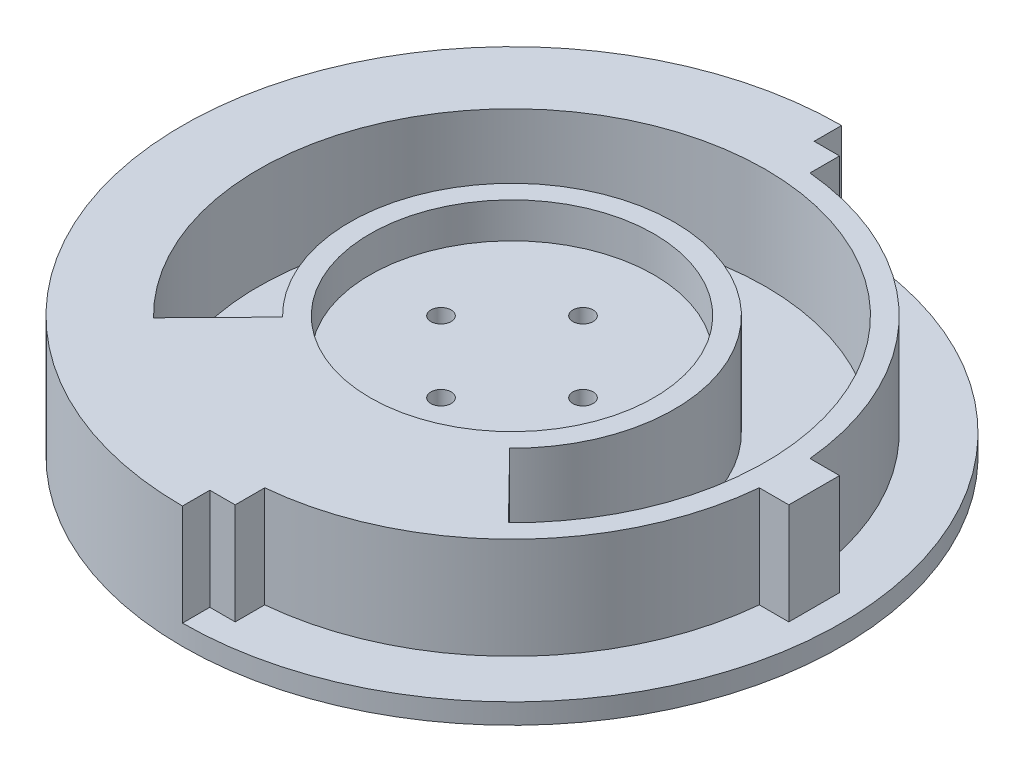
SolidWorks part; units mm, degrees
ref_plane "Front Plane" through (0, 0, 0) normal (0, 0, 1) x (1, 0, 0)
ref_plane "Top Plane" through (0, 0, 0) normal (0, 1, 0) x (1, 0, 0)
ref_plane "Right Plane" through (0, 0, 0) normal (1, 0, 0) x (0, 0, -1)
sketch "Sketch1" plane through (0, 0, 0) normal (0, 1, 0) x (1, 0, 0)
  line L0 (-17.5, -17.8536) -> (-11.2, -11.4263)
  line L1 (0, -55) -> (0, 55) construction
  line L2 (17.5, -17.8536) -> (11.2, -11.4263)
  line L4 (-17.5, -17.8536) -> (3.8221, -38.7535) construction
  circle A0 centre (0, 0) radius 27
  arc A1 (11.2, -11.4263) -> (-11.2, -11.4263) centre (0, 0) ccw
  arc A2 (17.5, -17.8536) -> (-17.5, -17.8536) centre (0, 0) ccw
  circle A3 centre (0, 0) radius 14
  arc A4 (16.5039, 11.7639) -> (14.35, -14.6399) centre (0.1913, -0.1952) cw construction
  circle A5 centre (0, 0) radius 19.9533 construction
  dimension "D1" = 54
  dimension "D2" = 2
  dimension "D3" = 9
  dimension "D4" = 2
  dimension "D5" = 35
extrude "Boss-Extrude1" add sketch "Sketch1" along normal blind 10
sketch "Sketch2" plane through (0, 0, 0) normal (0, -1, 0) x (1, 0, 0)
  circle A0 centre (0, 0) radius 32.5
  circle A1 centre (0, 0) radius 14 construction
  circle A2 centre (0, 0) radius 14 construction
  dimension "D1" = 65
extrude "Boss-Extrude2" add sketch "Sketch2" along normal blind 2
sketch "Sketch3" plane through (0, 0, 0) normal (0, 1, 0) x (1, 0, 0)
  line L0 (0, -5.5) -> (0, 5.5) construction
  line L1 (-2.5, 29.8) -> (2.5, 29.8)
  line L2 (-2.5, 29.8) -> (-2.5, 25.4032)
  line L3 (-2.5, 25.4032) -> (2.5, 25.4032)
  line L4 (2.5, 29.8) -> (2.5, 25.4032)
  line L5 (-2.5, 29.8) -> (2.5, 25.4032) construction
  line L6 (-2.5, 25.4032) -> (2.5, 29.8) construction
  line L7 (29.8, 2.5) -> (25.4032, 2.5)
  line L8 (29.8, 2.5) -> (29.8, -2.5)
  line L9 (29.8, -2.5) -> (25.4032, -2.5)
  line L10 (25.4032, 2.5) -> (25.4032, -2.5)
  line L11 (2.5, -29.8) -> (2.5, -25.4032)
  line L12 (2.5, -29.8) -> (-2.5, -29.8)
  line L13 (-2.5, -29.8) -> (-2.5, -25.4032)
  line L14 (2.5, -25.4032) -> (-2.5, -25.4032)
  line L15 (-29.8, -2.5) -> (-25.4032, -2.5)
  line L16 (-29.8, -2.5) -> (-29.8, 2.5)
  line L17 (-29.8, 2.5) -> (-25.4032, 2.5)
  line L18 (-25.4032, -2.5) -> (-25.4032, 2.5)
  circle A1 centre (0, 0) radius 27 construction
  point P0 (0, 27.6016)
  dimension "D2" = 29.8
  dimension "D1" = 5
  dimension "D3" = 4
extrude "Boss-Extrude3" add sketch "Sketch3" along normal blind 10
sketch "Sketch5" plane through (0, 0, 0) normal (0, 1, 0) x (1, 0, 0)
  line L0 (0, 29.8) -> (0, 32.5)
  line L1 (2.5, 29.8) -> (-2.5, 29.8) construction
  line L2 (0, -6.6) -> (0, 6.6) construction
  line L3 (0, -29.8) -> (0, -32.5)
  line L4 (0, 29.8) -> (-2.5, 29.8)
  line L5 (-2.5, 29.8) -> (-2.5, 26.884)
  line L6 (-26.884, 2.5) -> (-29.8, 2.5)
  line L7 (-29.8, 2.5) -> (-29.8, -2.5)
  line L8 (-29.8, -2.5) -> (-26.884, -2.5)
  line L9 (-2.5, -26.884) -> (-2.5, -29.8)
  line L10 (-2.5, -29.8) -> (0, -29.8)
  line L11 (-2.5, -29.8) -> (2.5, -29.8) construction
  circle A0 centre (0, 0) radius 32.5 construction
  arc A1 (0, 32.5) -> (0, -32.5) centre (0, 0) ccw
  arc A2 (-26.884, 2.5) -> (-2.5, 26.884) centre (0, 0) cw
  arc A3 (-26.884, -2.5) -> (-2.5, -26.884) centre (0, 0) ccw
extrude "Boss-Extrude4" add sketch "Sketch5" along normal up to surface (10 mm away) up to face at (0, 10, 0)
ref_plane "Plane1" through (0, 6.5, 0) normal (0, 1, 0) x (1, 0, 0)
sketch "Sketch6" plane through (0, 6.5, 0) normal (0, 1, 0) x (1, 0, 0)
  circle A0 centre (0, 0) radius 14
extrude "Boss-Extrude5" add sketch "Sketch6" against normal blind 2
sketch "Sketch4" plane through (0, -2, 0) normal (0, -1, 0) x (1, 0, 0)
  circle A0 centre (0, 0) radius 7 construction
  circle A1 centre (0, -7) radius 1
  circle A2 centre (-7, 0) radius 1
  circle A3 centre (0, 7) radius 1
  circle A4 centre (7, 0) radius 1
  point P14 (0, 0)
  dimension "D1" = 14
  dimension "D2" = 2
  dimension "D3" = 4
extrude "Cut-Extrude1" cut sketch "Sketch4" against normal through all both and the other way through all
